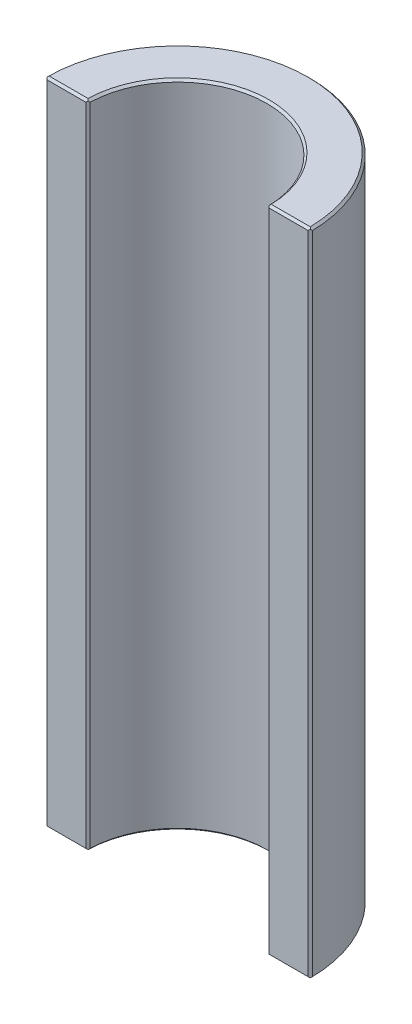
SolidWorks part; units mm, degrees
ref_plane "前视基准面" through (0, 0, 0) normal (0, 0, 1) x (1, 0, 0)
ref_plane "上视基准面" through (0, 0, 0) normal (0, 1, 0) x (1, 0, 0)
ref_plane "右视基准面" through (0, 0, 0) normal (1, 0, 0) x (0, 0, -1)
other "Configuration Table"
sketch "草图1" plane through (0, 0, 0) normal (0, 1, 0) x (1, 0, 0)
  line L0 (-24.5, 0) -> (-16.5, 0)
  line L1 (16.5, 0) -> (24.5, 0)
  arc A0 (16.5, 0) -> (-16.5, 0) centre (0, 0) ccw
  arc A1 (24.5, 0) -> (-24.5, 0) centre (0, 0) ccw
  circle A3 centre (0, 0) radius 24.5 construction
  circle A4 centre (0, 0) radius 16.5 construction
  point P4 (15.779, 4.8241)
  point P7 (24.5, 0)
  dimension "D1" = 33
  dimension "D2" = 8
extrude "凸台-拉伸1" add sketch "草图1" along normal blind 120
chamfer "倒角1" distance 0.4 angle 45 8 edges at (16.5, 60, 0) (20.5, 120, 0) (24.5, 60, 0) (20.5, 0, 0) (-24.5, 60, 0) (-20.5, 120, 0) (-16.5, 60, 0) (-20.5, 0, 0)
chamfer "倒角2" distance 0.4 angle 45 4 edges at (0, 0, -24.5) (0, 0, -16.5) (0, 120, -16.5) (0, 120, -24.5)
